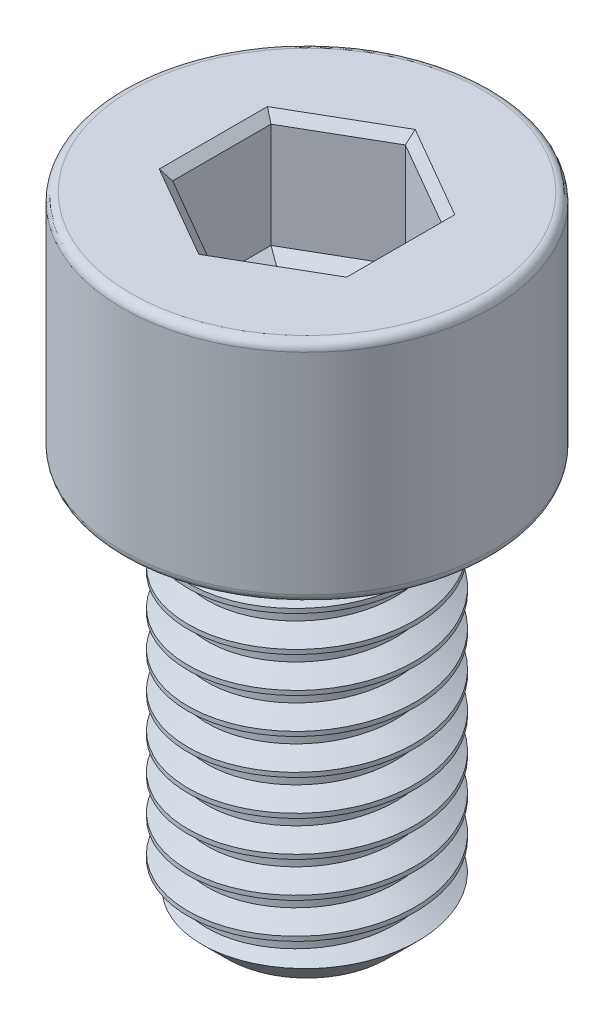
SolidWorks part; units mm, degrees
material "AISI Type A2 Tool Steel"
ref_plane "Front Plane" through (0, 0, 0) normal (0, 0, 1) x (1, 0, 0)
ref_plane "Top Plane" through (0, 0, 0) normal (0, 1, 0) x (1, 0, 0)
ref_plane "Right Plane" through (0, 0, 0) normal (1, 0, 0) x (0, 0, -1)
sketch "Sketch1" plane through (0, 0, 0) normal (0, 1, 0) x (1, 0, 0)
  circle A0 centre (0, 0) radius 4
  dimension "D1" = 8
extrude "Boss-Extrude1" add sketch "Sketch1" along normal blind 14
thread "Thread1" pitch 1.25 method cut profile "Thread Profile1" start angle 0, offset 1.25, length 0, pitch 1.25, diameter 8
ref_plane "Plane1" through (-4, 15.25, 0) normal (0, 0, 1) x (-1, 0, 0)
sketch "Thread Profile1" plane through (-4, 15.25, 0) normal (0, 0, 1) x (-1, 0, 0)
  line L0 (0, 0) -> (0, 1.25) construction
  line L11 (0, 0) -> (0, 1.0937)
  line L12 (0, 1.0937) -> (-0.6766, 0.7031)
  line L13 (-0.6766, 0.7031) -> (-0.6766, 0.3906)
  line L15 (-0.6766, 0.3906) -> (0, 0)
  line L17 (-0.6766, 0.5469) -> (0, 0.5469) construction
  point P2 (0, 0)
  dimension "Pitch" = 1.25
  dimension "Profile_Angle" = 60
  dimension "Profile_Land" = 0.3125
  dimension "Profile_Height" = 0.6766
sketch "Sketch2" plane through (0, 14, 0) normal (0, 1, 0) x (1, 0, 0)
  circle A0 centre (0, 0) radius 6.5
  dimension "D1" = 13
extrude "Boss-Extrude2" add sketch "Sketch2" along normal blind 8
sketch "Sketch5" plane through (0, 0, 0) normal (0, 0, 1) x (1, 0, 0)
  line L0 (0, 0) -> (0, 0.9986) construction
  line L1 (0, 0) -> (4.01, 0) construction
  line L2 (4.01, 0) -> (4.01, 1.2)
  line L3 (4.01, 1.2) -> (2.81, 0)
  line L4 (2.81, 0) -> (4.01, 0)
  dimension "D1" = 1.2
  dimension "D2" = 45
  dimension "D3" = 4.01
revolve "Cut-Revolve1" cut sketch "Sketch5" angle 360 about L0
fillet "Fillet1" radius 0.3 2 edges at (0, 22, 6.5) (0, 14, 6.5)
sketch "Sketch6" plane through (0, 22, 0) normal (0, 1, 0) x (1, 0, 0)
  line L1 (0, 3.4641) -> (-3, 1.7321)
  line L2 (-3, 1.7321) -> (-3, -1.7321)
  line L3 (-3, -1.7321) -> (0, -3.4641)
  line L4 (0, -3.4641) -> (3, -1.7321)
  line L5 (3, -1.7321) -> (3, 1.7321)
  line L6 (3, 1.7321) -> (0, 3.4641)
  circle A0 centre (0, 0) radius 3 construction
  dimension "D1" = 6
extrude "Cut-Extrude1" cut sketch "Sketch6" against normal blind 4
chamfer "Chamfer1" distance 0.3 angle 45 6 edges at (-3, 22, 0) (-1.5, 22, 2.5981) (1.5, 22, 2.5981) (3, 22, 0) (1.5, 22, -2.5981) (-1.5, 22, -2.5981)
sketch "Sketch7" plane through (0, 18, 0) normal (0, 1, 0) x (1, 0, 0)
  line L1 (0, 3.4641) -> (-3, 1.7321)
  line L2 (-3, 1.7321) -> (-3, -1.7321)
  line L3 (-3, -1.7321) -> (0, -3.4641)
  line L4 (0, -3.4641) -> (3, -1.7321)
  line L5 (3, -1.7321) -> (3, 1.7321)
  line L6 (3, 1.7321) -> (0, 3.4641)
  circle A0 centre (0, 0) radius 3 construction
extrude "Cut-Extrude2" cut sketch "Sketch7" against normal blind 0.4 draft 60
